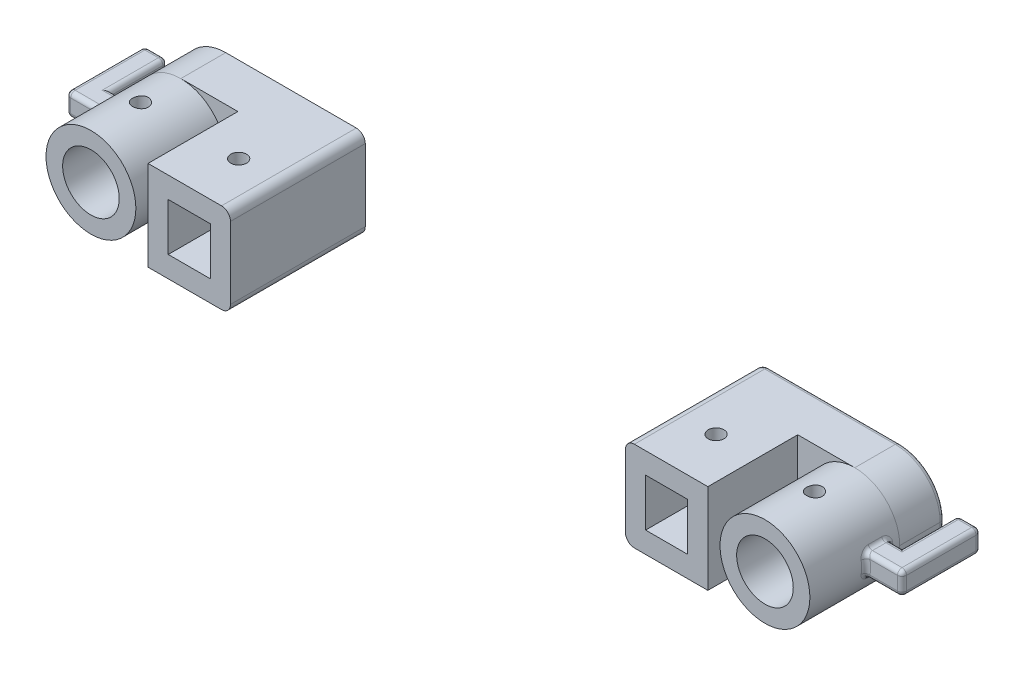
SolidWorks part; units mm, degrees
ref_plane "Front Plane" through (0, 0, 0) normal (0, 0, 1) x (1, 0, 0)
ref_plane "Top Plane" through (0, 0, 0) normal (0, 1, 0) x (1, 0, 0)
ref_plane "Right Plane" through (0, 0, 0) normal (1, 0, 0) x (0, 0, -1)
sketch "Sketch1" plane through (0, 0, 0) normal (0, 0, 1) x (1, 0, 0)
  line L1 (-85, 10) -> (85, 10)
  line L2 (-85, 10) -> (-85, -10)
  line L3 (-85, -10) -> (85, -10)
  line L4 (85, 10) -> (85, -10)
  line L5 (-85, 10) -> (85, -10) construction
  line L6 (-85, -10) -> (85, 10) construction
  point P0 (0, 0)
  dimension "D1" = 170
  dimension "D2" = 20
extrude "Boss-Extrude1" add sketch "Sketch1" along normal blind 10
sketch "Sketch2" plane through (0, 0, 10) normal (0, 0, 1) x (1, 0, 0)
  line L1 (-57.795, 5.3) -> (-48.445, 5.3)
  line L2 (-57.795, 5.3) -> (-57.795, -5.3)
  line L3 (-57.795, -5.3) -> (-48.445, -5.3)
  line L4 (-48.445, 5.3) -> (-48.445, -5.3)
  line L5 (-57.795, 5.3) -> (-48.445, -5.3) construction
  line L6 (-57.795, -5.3) -> (-48.445, 5.3) construction
  line L7 (48.445, 5.3) -> (57.795, 5.3)
  line L8 (48.445, 5.3) -> (48.445, -5.3)
  line L9 (48.445, -5.3) -> (57.795, -5.3)
  line L10 (57.795, 5.3) -> (57.795, -5.3)
  line L11 (48.445, 5.3) -> (57.795, -5.3) construction
  line L12 (48.445, -5.3) -> (57.795, 5.3) construction
  line L13 (85, 10) -> (-85, 10) construction
  line L14 (-85, -10) -> (85, -10) construction
  line L16 (-62.295, 10) -> (-43.945, 10)
  line L17 (-62.295, 10) -> (-62.295, -10)
  line L18 (-62.295, -10) -> (-43.945, -10)
  line L19 (-43.945, 10) -> (-43.945, -10)
  line L20 (-62.295, 10) -> (-43.945, -10) construction
  line L21 (-62.295, -10) -> (-43.945, 10) construction
  line L22 (43.945, 10) -> (62.295, 10)
  line L23 (43.945, 10) -> (43.945, -10)
  line L24 (43.945, -10) -> (62.295, -10)
  line L25 (62.295, 10) -> (62.295, -10)
  line L26 (43.945, 10) -> (62.295, -10) construction
  line L27 (43.945, -10) -> (62.295, 10) construction
  circle A0 centre (-75, 0) radius 6.3
  circle A1 centre (75, 0) radius 6.3
  circle A2 centre (-75, 0) radius 10
  circle A3 centre (75, 0) radius 10
  point P2 (-53.12, 0)
  point P7 (53.12, 0)
  point P22 (-53.12, 0)
  point P27 (53.12, 0)
  dimension "D2" = 12.6
  dimension "D4" = 20
  dimension "D1" = 10.6
  dimension "D3" = 9.35
  dimension "D5" = 75
  dimension "D6" = 75
  dimension "D7" = 21.88
  dimension "D8" = 21.88
  dimension "D9" = 10
  dimension "D10" = 4.5
extrude "Boss-Extrude2" add sketch "Sketch2" along normal blind 20
sketch "Sketch3" plane through (0, 10, 0) normal (0, 1, 0) x (1, 0, 0)
  line L0 (-81.3, -10) -> (-68.7, -10) construction
  circle A0 centre (-53.12, -19) radius 1.75
  circle A1 centre (-75, -19) radius 1.75
  circle A2 centre (53.12, -19) radius 1.75
  circle A3 centre (75, -19) radius 1.75
  dimension "D1" = 3.5
  dimension "D2" = 9
extrude "Cut-Extrude1" cut sketch "Sketch3" against normal through all both and the other way through all
sketch "Sketch4" plane through (0, 0, 10) normal (0, 0, 1) x (1, 0, 0)
  line L0 (-75, -10) -> (-62.295, -10) construction
  line L1 (-43.945, -10) -> (43.945, -10)
  line L2 (-43.945, -10) -> (-43.945, 40)
  line L3 (-43.945, 40) -> (43.945, 40)
  line L4 (43.945, -10) -> (43.945, 40)
  dimension "D3" = 50
extrude "Cut-Extrude2" cut sketch "Sketch4" against normal through all
fillet "Fillet2" radius 2 2 edges at (-43.945, -10, 15) (-43.945, 10, 15)
fillet "Fillet4" radius 2 2 edges at (43.945, 10, 15) (43.945, -10, 15)
sketch "Sketch8" plane through (-85, 0, 0) normal (-1, 0, 0) x (0, 0, 1)
  line L0 (10, 0) -> (10, -10) construction
  line L6 (12.5, 2.5) -> (17.5, 2.5)
  line L8 (12.5, 2.5) -> (12.5, -2.5)
  line L9 (12.5, -2.5) -> (17.5, -2.5)
  line L10 (17.5, 2.5) -> (17.5, -2.5)
  line L11 (12.5, 2.5) -> (17.5, -2.5) construction
  line L12 (12.5, -2.5) -> (17.5, 2.5) construction
  point P0 (15, 0)
  point P5 (0, 0)
  point P6 (17.377, 0)
  point P7 (0, 0)
  point P8 (0, 0)
  point P9 (0, 0)
  dimension "D1" = 5
  dimension "D2" = 5
  dimension "D3" = 5
extrude "Boss-Extrude5" add sketch "Sketch8" along normal blind 8 and the other way blind 2
sketch "Sketch9" plane through (0, 0, 12.5) normal (0, 0, -1) x (-1, 0, 0)
  line L5 (93, -2.5) -> (84.6825, -2.5) construction
  line L6 (93, 2.5) -> (88, 2.5)
  line L7 (93, 2.5) -> (93, -2.5)
  line L8 (93, -2.5) -> (88, -2.5)
  line L9 (88, 2.5) -> (88, -2.5)
  dimension "D1" = 5
extrude "Boss-Extrude6" add sketch "Sketch9" along normal up to surface (12.5 mm away) up to face at (-58.1586, 0, 0)
sketch "Sketch10" plane through (85, 0, 0) normal (1, 0, 0) x (0, 0, -1)
  line L0 (-10, 10) -> (-10, 0) construction
  line L1 (-17.5, 2.5) -> (-12.5, 2.5)
  line L2 (-17.5, 2.5) -> (-17.5, -2.5)
  line L3 (-17.5, -2.5) -> (-12.5, -2.5)
  line L4 (-12.5, 2.5) -> (-12.5, -2.5)
  line L5 (-17.5, 2.5) -> (-12.5, -2.5) construction
  line L6 (-17.5, -2.5) -> (-12.5, 2.5) construction
  point P0 (-15, 0)
  point P5 (0, 0)
  dimension "D1" = 5
  dimension "D2" = 5
  dimension "D3" = 5
extrude "Boss-Extrude7" add sketch "Sketch10" along normal blind 8 and the other way blind 3
sketch "Sketch12" plane through (0, 0, 12.5) normal (0, 0, -1) x (-1, 0, 0)
  line L0 (-84.6825, -2.5) -> (-93, -2.5) construction
  line L1 (-93, 2.5) -> (-88, 2.5)
  line L2 (-93, 2.5) -> (-93, -2.5)
  line L3 (-93, -2.5) -> (-88, -2.5)
  line L4 (-88, 2.5) -> (-88, -2.5)
  dimension "D1" = 5
extrude "Boss-Extrude8" add sketch "Sketch12" along normal up to surface (12.5 mm away) up to face at (58.1586, 0, 0)
fillet "Fillet7" radius 10 7 edges at (-85, -10, 5) (-80, -10, 10) (-85, -5, 10) (-85, 5, 10) (-80, 10, 10) (-85, 0, 0) (-85, 10, 5)
fillet "Fillet8" radius 10 2 edges at (85, -10, 5) (85, 10, 5)
fillet "Fillet9" radius 1 16 edges at (85, 0, 12.5) (85, 0, 17.5) (88.8412, -2.5, 17.5) (93, -2.5, 8.75) (88, -2.5, 6.25) (86.3412, -2.5, 12.5) (84.6825, -2.5, 15) (86.3412, 2.5, 12.5) (88, 2.5, 6.25) (93, 2.5, 8.75) (88.8412, 2.5, 17.5) (84.6825, 2.5, 15) (93, 0, 0) (90.5, 2.5, 0) (88, 0, 0) (90.5, -2.5, 0)
fillet "Fillet10" radius 1 16 edges at (-85, 0, 17.5) (-85, 0, 12.5) (-93, 0, 0) (-88, 0, 0) (-86.3412, -2.5, 12.5) (-88, -2.5, 6.25) (-90.5, -2.5, 0) (-93, -2.5, 8.75) (-88.8412, -2.5, 17.5) (-84.6825, -2.5, 15) (-88.8412, 2.5, 17.5) (-93, 2.5, 8.75) (-90.5, 2.5, 0) (-88, 2.5, 6.25) (-86.3412, 2.5, 12.5) (-84.6825, 2.5, 15)
fillet "Fillet11" radius 1 7 edges at (60.4725, 10, 0) (44.5308, 9.4142, 0) (43.945, 0, 0) (44.5308, -9.4142, 0) (60.4725, -10, 0) (82.0711, -7.0711, 0) (82.0711, 7.0711, 0)
fillet "Fillet12" radius 1 3 edges at (92.7071, 2.2071, 17.2071) (92.7071, -2.2071, 17.2071) (93, 0, 17.5)
fillet "Fillet13" radius 1 3 edges at (-92.7071, -2.2071, 17.2071) (-92.7071, 2.2071, 17.2071) (-93, 0, 17.5)
